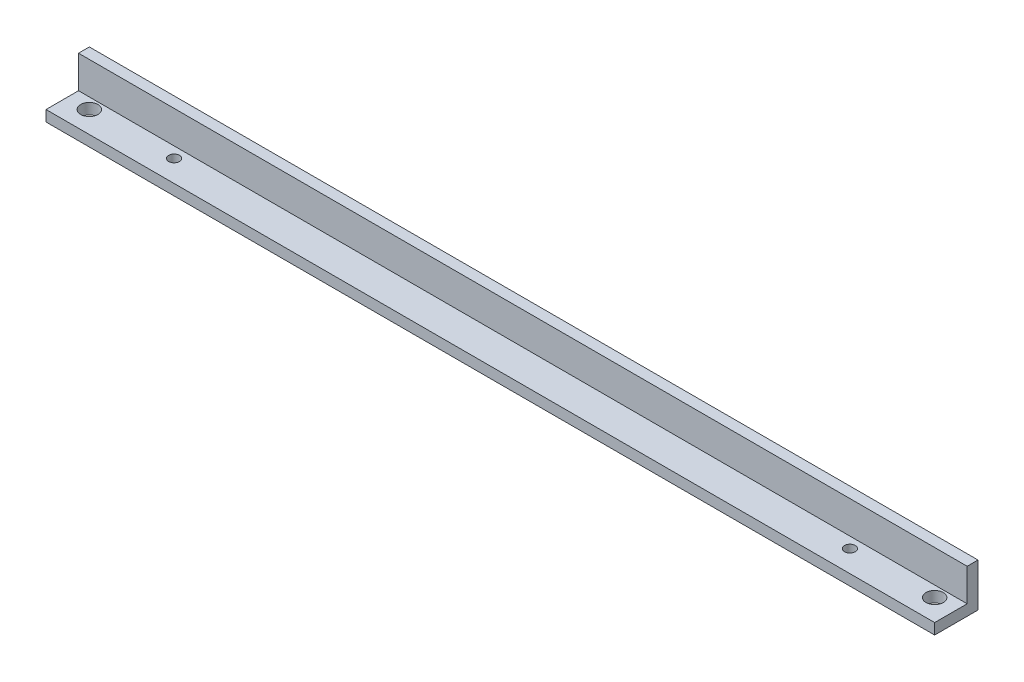
SolidWorks part; units mm, degrees
material "6061-T6 (SS)"
ref_plane "Front Plane" through (0, 0, 0) normal (0, 0, 1) x (1, 0, 0)
ref_plane "Top Plane" through (0, 0, 0) normal (0, 1, 0) x (1, 0, 0)
ref_plane "Right Plane" through (0, 0, 0) normal (1, 0, 0) x (0, 0, -1)
sketch "Sketch1" plane through (0, 0, 0) normal (1, 0, 0) x (0, 0, -1)
  line L0 (0, 0) -> (0, 19.05)
  line L1 (0, 19.05) -> (6.35, 19.05)
  line L2 (6.35, 19.05) -> (6.35, -6.35)
  line L3 (6.35, -6.35) -> (-19.05, -6.35)
  line L4 (-19.05, -6.35) -> (-19.05, 0)
  line L5 (-19.05, 0) -> (0, 0)
  dimension "D1" = 25.4
  dimension "D2" = 25.4
  dimension "D3" = 6.35
  dimension "D4" = 6.35
extrude "Boss-Extrude1" add sketch "Sketch1" along normal blind 520.7
sketch "Sketch2" plane through (0, -6.35, 0) normal (0, -1, 0) x (1, 0, 0)
  line L0 (0, 6.35) -> (520.7, 6.35) construction
  line L1 (0, 19.05) -> (0, -6.35) construction
  line L2 (260.35, 19.05) -> (260.35, -6.35) construction
  line L5 (520.7, 19.05) -> (520.7, -6.35) construction
  line L6 (520.7, 19.05) -> (0, 19.05) construction
  line L7 (520.7, -6.35) -> (0, -6.35) construction
  circle A0 centre (12.7, 6.35) radius 5.08
  circle A1 centre (62.357, 6.35) radius 3.175
  circle A8 centre (458.343, 6.35) radius 3.175
  circle A9 centre (508, 6.35) radius 5.08
  dimension "D1" = 10.16
  dimension "D2" = 6.35
  dimension "D3" = 12.7
  dimension "D4" = 49.657
extrude "Cut-Extrude1" cut sketch "Sketch2" against normal blind 914.4
